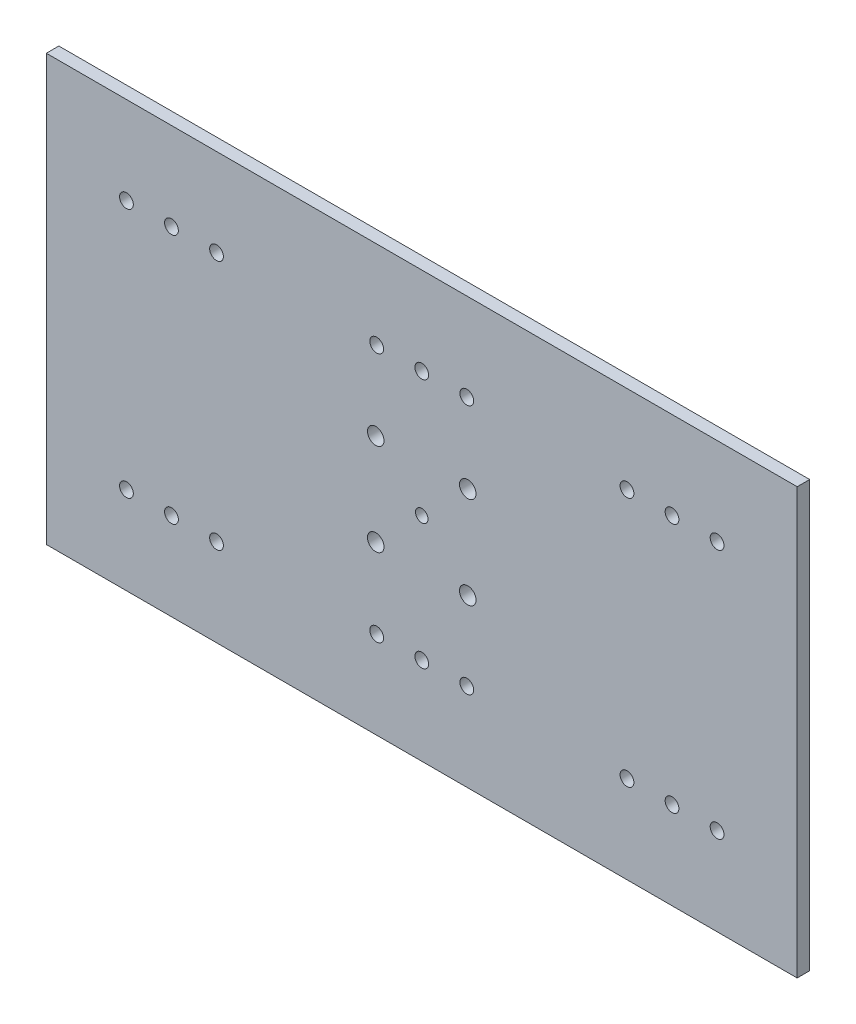
SolidWorks part; units mm, degrees
ref_plane "前视基准面" through (0, 0, 0) normal (0, 0, 1) x (1, 0, 0)
ref_plane "上视基准面" through (0, 0, 0) normal (0, 1, 0) x (1, 0, 0)
ref_plane "右视基准面" through (0, 0, 0) normal (1, 0, 0) x (0, 0, -1)
sketch "草图1" plane through (0, 0, 0) normal (0, 0, 1) x (1, 0, 0)
  line L0 (-18.3848, 18.3848) -> (0, 0) construction
  line L1 (150, -125) -> (-150, -125)
  line L2 (150, -125) -> (150, 125)
  line L3 (150, 125) -> (-150, 125)
  line L4 (-150, -125) -> (-150, 125)
  line L5 (150, -125) -> (-150, 125) construction
  line L6 (150, 125) -> (-150, -125) construction
  line L7 (0, 0) -> (0, 75.2853) construction
  line L8 (0, 0) -> (89.5261, 0) construction
  circle A0 centre (-18.3848, 18.3848) radius 3.3
  circle A1 centre (18.3848, 18.3848) radius 3.3
  circle A2 centre (18.3848, -18.3848) radius 3.3
  circle A3 centre (-18.3848, -18.3848) radius 3.3
  circle A4 centre (0, 0) radius 2.5
  point P0 (0, 0)
  dimension "D3" = 6.6
  dimension "D6" = 5
  dimension "D1" = 250
  dimension "D2" = 300
  dimension "D4" = 26
  dimension "D5" = 45
extrude "凸台-拉伸1" add sketch "草图1" along normal blind 5
sketch "草图2" plane through (0, 0, 5) normal (0, 0, 1) x (1, 0, 0)
  line L0 (-150, 0) -> (150, 0) construction
  line L1 (-150, 125) -> (-150, -125) construction
  line L2 (150, -125) -> (150, 125) construction
  line L3 (0, 125) -> (0, -125) construction
  line L4 (150, 125) -> (-150, 125) construction
  line L5 (-150, -125) -> (150, -125) construction
  line L7 (100, -50) -> (-100, -50) construction
  line L8 (100, -50) -> (100, 50) construction
  line L9 (100, 50) -> (-100, 50) construction
  line L10 (-100, -50) -> (-100, 50) construction
  line L11 (100, -50) -> (-100, 50) construction
  line L12 (100, 50) -> (-100, -50) construction
  circle A0 centre (-100, 50) radius 2.75
  circle A1 centre (0, 50) radius 2.75
  circle A2 centre (100, 50) radius 2.75
  circle A3 centre (100, -50) radius 2.75
  circle A4 centre (0, -50) radius 2.75
  circle A5 centre (-100, -50) radius 2.75
  circle A6 centre (-118, 50) radius 2.75
  circle A7 centre (-82, 50) radius 2.75
  circle A8 centre (-82, -50) radius 2.75
  circle A9 centre (-118, -50) radius 2.75
  circle A10 centre (-18, 50) radius 2.75
  circle A11 centre (-18, -50) radius 2.75
  circle A12 centre (118, -50) radius 2.75
  circle A13 centre (82, -50) radius 2.75
  circle A14 centre (18, -50) radius 2.75
  circle A15 centre (18, 50) radius 2.75
  circle A16 centre (82, 50) radius 2.75
  circle A17 centre (118, 50) radius 2.75
  point P12 (0, 0)
  point P26 (-118, 50)
  dimension "D1" = 5.5
  dimension "D4" = 5.5
  dimension "D6" = 5.5
  dimension "D7" = 18
  dimension "D2" = 100
  dimension "D3" = 200
  dimension "D5" = 18
extrude "切除-拉伸1" cut sketch "草图2" against normal through all
sketch "草图3" plane through (0, 0, 5) normal (0, 0, 1) x (1, 0, 0)
  line L0 (-150, 125) -> (-150, -125) construction
  line L1 (150, -85) -> (-150, -85) construction
  line L3 (150, 85) -> (-150, 85) construction
  line L5 (150, -85) -> (-150, 85) construction
  line L6 (150, 85) -> (-150, -85) construction
  line L7 (150, 125) -> (-150, 125) construction
  line L9 (-150, 125) -> (150, 125)
  line L10 (-150, 125) -> (-150, 85)
  line L11 (-150, 85) -> (150, 85)
  line L12 (150, 125) -> (150, 85)
  line L13 (-150, -85) -> (150, -85)
  line L14 (-150, -85) -> (-150, -125)
  line L15 (-150, -125) -> (150, -125)
  line L16 (150, -85) -> (150, -125)
  point P0 (0, 0)
  dimension "D1" = 40
extrude "切除-拉伸2" cut sketch "草图3" against normal through all contours L10 L9 L12 L11 | L14 L13 L16 L15
